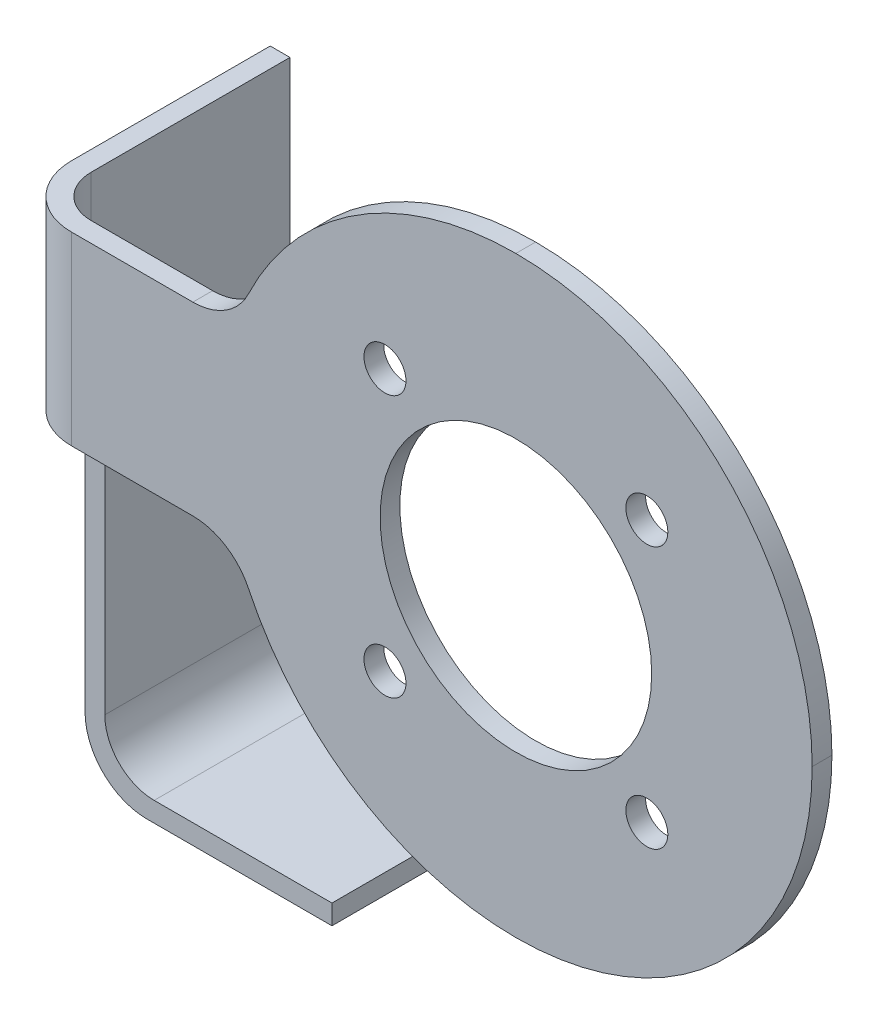
SolidWorks part; units mm, degrees
ref_plane "Front Plane" through (0, 0, 0) normal (0, 0, 1) x (1, 0, 0)
ref_plane "Top Plane" through (0, 0, 0) normal (0, 1, 0) x (1, 0, 0)
ref_plane "Right Plane" through (0, 0, 0) normal (1, 0, 0) x (0, 0, -1)
sketch "Sketch2" plane through (0, 0, 0) normal (0, 1, 0) x (1, 0, 0)
  line L0 (0, 0) -> (-60, 0)
  line L1 (-65, 5) -> (-65, 21.1)
  line L2 (-65, 21.1) -> (-63.4, 21.1)
  line L3 (-63.4, 21.1) -> (-63.4, 5)
  line L4 (-60, 1.6) -> (0, 1.6)
  line L5 (0, 1.6) -> (0, 0)
  arc A0 (-60, 0) -> (-65, 5) centre (-60, 5) cw
  arc A1 (-63.4, 5) -> (-60, 1.6) centre (-60, 5) ccw
  point P9 (-65, 0)
  dimension "D4" = 5
  dimension "D1" = 1.6
  dimension "D2" = 65
  dimension "D3" = 21.1
extrude "Boss-Extrude1" add sketch "Sketch2" along normal blind 48
sketch "Sketch4" plane through (0, 0, 0) normal (0, 0, 1) x (1, 0, 0)
  line L0 (-24, 48) -> (-24, 24) construction
  line L1 (-60, 48) -> (0, 48) construction
  line L2 (-24, 24) -> (0, 24) construction
  line L3 (0, 48) -> (0, 0) construction
  circle A0 centre (-24, 24) radius 11
  dimension "D1" = 22
extrude "Cut-Extrude1" cut sketch "Sketch4" against normal through all
sketch "Sketch3" plane through (0, 0, -21.1) normal (0, 0, -1) x (-1, 0, 0)
  line L0 (63.4, 0) -> (63.4, -7.12)
  line L1 (59.4, -11.12) -> (45, -11.12)
  line L2 (45, -11.12) -> (45, -12.72)
  line L3 (45, -12.72) -> (60, -12.72)
  line L4 (65, -7.72) -> (65, 0)
  line L5 (65, 48) -> (65, 0) construction
  line L7 (63.4, 0) -> (65, 0) construction
  line L8 (63.4, 0) -> (65, 0)
  line L9 (65, 24) -> (0, 24) construction
  line L10 (0, 48) -> (0, 0) construction
  arc A0 (63.4, -7.12) -> (59.4, -11.12) centre (59.4, -7.12) cw
  arc A1 (60, -12.72) -> (65, -7.72) centre (60, -7.72) ccw
  point P20 (65, -12.72)
  dimension "D3" = 4
  dimension "D4" = 5
  dimension "D1" = 36.72
  dimension "D2" = 20
extrude "Boss-Extrude2" add sketch "Sketch3" against normal blind 15
hole_wizard "M3 Clearance Hole2" positions "Sketch5" profile "Sketch6" hole size "M3" standard "ANSI Metric" end condition through all
sketch "Sketch5" plane through (0, 0, 0) normal (0, 0, 1) x (1, 0, 0)
  line L0 (-34.6066, 34.6066) -> (-13.3934, 13.3934) construction
  line L3 (-34.6066, 13.3934) -> (-13.3934, 34.6066) construction
  circle A0 centre (-24, 24) radius 15 construction
  point P5 (-34.6066, 34.6066)
  point P7 (-13.3934, 34.6066)
  point P9 (-13.3934, 13.3934)
  point P11 (-34.6066, 13.3934)
  dimension "D1" = 30
  dimension "D2" = 90
sketch "Sketch6" plane through (-34.6066, 13.3934, 0) normal (1, 0, 0) x (0, -1, 0)
  line L0 (0, 0) -> (0, 21.1)
  line L1 (0, 21.1) -> (1.7, 21.1)
  line L2 (1.7, 21.1) -> (1.7, 0)
  line L5 (1.7, 0) -> (0, 0)
  line L11 (0, -6.35) -> (0, 107.95) construction
  dimension "Thru Hole Dia." = 3.4
  dimension "Thru Hole Depth" = 21.1
sketch "Sketch8" plane through (0, 0, 0) normal (0, 0, 1) x (1, 0, 0)
  line L0 (-24, 0) -> (-65, 0)
  line L1 (-65, 0) -> (-65, 16.5)
  line L2 (-65, 48) -> (-65, 0) construction
  line L3 (-65, 16.5) -> (-46.798, 16.5)
  line L4 (-24, 24) -> (-65, 24) construction
  arc A0 (-46.798, 16.5) -> (-24, 0) centre (-24, 24) ccw
  point P1 (0, 0)
  dimension "D1" = 7.5
extrude "Cut-Extrude2" cut sketch "Sketch8" against normal up to surface (6.1 mm away) up to face at (-58.508, -8.048, -6.1)
sketch "Sketch9" plane through (0, 0, 0) normal (0, 0, 1) x (1, 0, 0)
  line L0 (-24, 48) -> (-65, 48)
  line L1 (-65, 48) -> (-65, 31.5)
  line L2 (-65, 48) -> (-65, 16.5) construction
  line L3 (-65, 31.5) -> (-46.798, 31.5)
  line L4 (-24, 24) -> (-65, 24) construction
  arc A0 (-24, 48) -> (-46.798, 31.5) centre (-24, 24) ccw
  point P1 (0, 0)
  dimension "D1" = 7.5
extrude "Cut-Extrude3" cut sketch "Sketch9" against normal up to surface (21.1 mm away) up to face at (-58.508, 3.952, -21.1)
fillet "Fillet1" radius 24 2 edges at (0, 0, -0.8) (0, 48, -0.8)
fillet "Fillet2" radius 5 2 edges at (-46.798, 16.5, -0.8) (-46.798, 31.5, -0.8)
